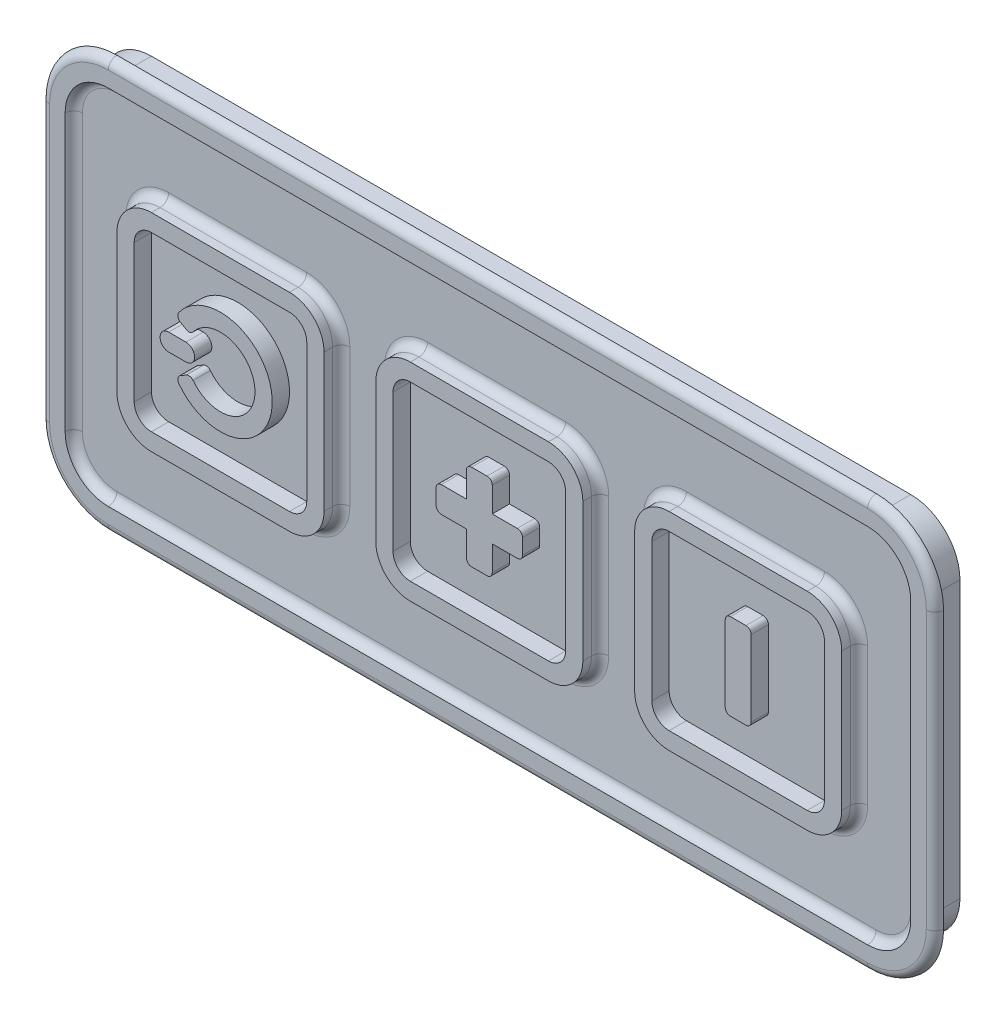
SolidWorks part; units mm, degrees
ref_plane "前视基准面" through (0, 0, 0) normal (0, 0, 1) x (1, 0, 0)
ref_plane "上视基准面" through (0, 0, 0) normal (0, 1, 0) x (1, 0, 0)
ref_plane "右视基准面" through (0, 0, 0) normal (1, 0, 0) x (0, 0, -1)
sketch "草图1" plane through (0, 0, 0) normal (0, 0, 1) x (1, 0, 0)
  line L8 (26.456, 8) -> (26.456, -8)
  line L9 (29.356, -10.9) -> (73.356, -10.9)
  line L10 (76.256, -8) -> (76.256, 8)
  line L11 (73.356, 10.9) -> (29.356, 10.9)
  arc A8 (26.456, -8) -> (29.356, -10.9) centre (29.356, -8) ccw
  arc A9 (73.356, -10.9) -> (76.256, -8) centre (73.356, -8) ccw
  arc A10 (76.256, 8) -> (73.356, 10.9) centre (73.356, 8) ccw
  arc A11 (29.356, 10.9) -> (26.456, 8) centre (29.356, 8) ccw
extrude "凸台-拉伸1" add sketch "草图1" against normal blind 2
sketch "草图2" plane through (0, 0, 0) normal (0, 0, 1) x (1, 0, 0)
  line L4 (26.856, 8) -> (26.856, -8)
  line L5 (29.356, -10.5) -> (73.356, -10.5)
  line L6 (75.856, -8) -> (75.856, 8)
  line L7 (73.356, 10.5) -> (29.356, 10.5)
  line L8 (25.456, 8) -> (25.456, -8)
  line L9 (25.456, 8) -> (25.456, -8)
  line L10 (29.356, -11.9) -> (73.356, -11.9)
  line L11 (29.356, -11.9) -> (73.356, -11.9)
  line L20 (25.356, 8) -> (25.356, -8) construction
  line L21 (29.356, -12) -> (73.356, -12) construction
  line L22 (77.356, -8) -> (77.356, 8) construction
  line L23 (73.356, 12) -> (29.356, 12) construction
  line L24 (77.256, -8) -> (77.256, 8)
  line L25 (77.256, -8) -> (77.256, 8)
  line L26 (73.356, 11.9) -> (29.356, 11.9)
  line L27 (73.356, 11.9) -> (29.356, 11.9)
  arc A4 (26.856, -8) -> (29.356, -10.5) centre (29.356, -8) ccw
  arc A5 (73.356, -10.5) -> (75.856, -8) centre (73.356, -8) ccw
  arc A6 (75.856, 8) -> (73.356, 10.5) centre (73.356, 8) ccw
  arc A7 (29.356, 10.5) -> (26.856, 8) centre (29.356, 8) ccw
  arc A8 (29.356, 11.9) -> (25.456, 8) centre (29.356, 8) ccw
  arc A9 (29.356, 11.9) -> (25.456, 8) centre (29.356, 8) ccw
  arc A10 (25.456, -8) -> (29.356, -11.9) centre (29.356, -8) ccw
  arc A11 (25.456, -8) -> (29.356, -11.9) centre (29.356, -8) ccw
  arc A20 (29.356, 12) -> (25.356, 8) centre (29.356, 8) ccw construction
  arc A21 (25.356, -8) -> (29.356, -12) centre (29.356, -8) ccw construction
  arc A22 (73.356, -12) -> (77.356, -8) centre (73.356, -8) ccw construction
  arc A23 (77.356, 8) -> (73.356, 12) centre (73.356, 8) ccw construction
  arc A24 (73.356, -11.9) -> (77.256, -8) centre (73.356, -8) ccw
  arc A25 (73.356, -11.9) -> (77.256, -8) centre (73.356, -8) ccw
  arc A26 (77.256, 8) -> (73.356, 11.9) centre (73.356, 8) ccw
  arc A27 (77.256, 8) -> (73.356, 11.9) centre (73.356, 8) ccw
  dimension "D1" = 1
  dimension "D2" = 1.5
extrude "凸台-拉伸2" add sketch "草图2" along normal blind 0.5
sketch "草图3" plane through (0, 0, -2) normal (0, 0, -1) x (-1, 0, 0)
  line L8 (-29.356, 9.9) -> (-73.356, 9.9)
  line L9 (-29.356, 9.9) -> (-73.356, 9.9)
  line L10 (-75.256, 8) -> (-75.256, -8)
  line L11 (-75.256, 8) -> (-75.256, -8)
  line L16 (-73.356, -9.9) -> (-29.356, -9.9)
  line L17 (-73.356, -9.9) -> (-29.356, -9.9)
  line L18 (-27.456, -8) -> (-27.456, 8)
  line L19 (-27.456, -8) -> (-27.456, 8)
  arc A8 (-27.456, 8) -> (-29.356, 9.9) centre (-29.356, 8) ccw
  arc A9 (-27.456, 8) -> (-29.356, 9.9) centre (-29.356, 8) ccw
  arc A10 (-73.356, 9.9) -> (-75.256, 8) centre (-73.356, 8) ccw
  arc A11 (-73.356, 9.9) -> (-75.256, 8) centre (-73.356, 8) ccw
  arc A16 (-75.256, -8) -> (-73.356, -9.9) centre (-73.356, -8) ccw
  arc A17 (-75.256, -8) -> (-73.356, -9.9) centre (-73.356, -8) ccw
  arc A18 (-29.356, -9.9) -> (-27.456, -8) centre (-29.356, -8) ccw
  arc A19 (-29.356, -9.9) -> (-27.456, -8) centre (-29.356, -8) ccw
  dimension "D1" = 1
extrude "切除-拉伸1" cut sketch "草图3" against normal blind 1
sketch "草图4" plane through (0, 0, 0) normal (0, 0, 1) x (1, 0, 0)
  line L0 (27.356, 0) -> (75.356, 0) construction
  line L3 (32.356, 6) -> (40.356, 6)
  line L4 (32.356, 5) -> (40.356, 5)
  line L5 (31.356, 4) -> (31.356, -4)
  line L6 (32.356, -5) -> (40.356, -5)
  line L7 (41.356, 4) -> (41.356, -4)
  line L8 (31.356, 5) -> (41.356, -5) construction
  line L9 (31.356, -5) -> (41.356, 5) construction
  line L10 (47.356, 5) -> (55.356, 5)
  line L11 (46.356, 4) -> (46.356, -4)
  line L12 (47.356, -5) -> (55.356, -5)
  line L13 (56.356, 4) -> (56.356, -4)
  line L14 (46.356, 5) -> (56.356, -5) construction
  line L15 (46.356, -5) -> (56.356, 5) construction
  line L16 (62.356, 5) -> (70.356, 5)
  line L17 (61.356, 4) -> (61.356, -4)
  line L18 (62.356, -5) -> (70.356, -5)
  line L19 (71.356, 4) -> (71.356, -4)
  line L20 (61.356, 5) -> (71.356, -5) construction
  line L21 (61.356, -5) -> (71.356, 5) construction
  line L22 (42.356, 4) -> (42.356, -4)
  line L23 (32.356, -6) -> (40.356, -6)
  line L24 (30.356, 4) -> (30.356, -4)
  line L25 (47.356, 6) -> (55.356, 6)
  line L26 (57.356, 4) -> (57.356, -4)
  line L27 (47.356, -6) -> (55.356, -6)
  line L28 (45.356, 4) -> (45.356, -4)
  line L29 (62.356, 6) -> (70.356, 6)
  line L30 (72.356, 4) -> (72.356, -4)
  line L31 (62.356, -6) -> (70.356, -6)
  line L32 (60.356, 4) -> (60.356, -4)
  arc A0 (70.356, 5) -> (71.356, 4) centre (70.356, 4) cw
  arc A1 (70.356, -5) -> (71.356, -4) centre (70.356, -4) ccw
  arc A2 (61.356, -4) -> (62.356, -5) centre (62.356, -4) ccw
  arc A3 (62.356, 5) -> (61.356, 4) centre (62.356, 4) ccw
  arc A4 (55.356, 5) -> (56.356, 4) centre (55.356, 4) cw
  arc A5 (55.356, -5) -> (56.356, -4) centre (55.356, -4) ccw
  arc A6 (46.356, -4) -> (47.356, -5) centre (47.356, -4) ccw
  arc A7 (47.356, 5) -> (46.356, 4) centre (47.356, 4) ccw
  arc A8 (40.356, 5) -> (41.356, 4) centre (40.356, 4) cw
  arc A9 (40.356, -5) -> (41.356, -4) centre (40.356, -4) ccw
  arc A10 (31.356, -4) -> (32.356, -5) centre (32.356, -4) ccw
  arc A11 (32.356, 5) -> (31.356, 4) centre (32.356, 4) ccw
  arc A12 (40.356, 6) -> (42.356, 4) centre (40.356, 4) cw
  arc A13 (40.356, -6) -> (42.356, -4) centre (40.356, -4) ccw
  arc A14 (30.356, -4) -> (32.356, -6) centre (32.356, -4) ccw
  arc A15 (32.356, 6) -> (30.356, 4) centre (32.356, 4) ccw
  arc A16 (55.356, 6) -> (57.356, 4) centre (55.356, 4) cw
  arc A17 (55.356, -6) -> (57.356, -4) centre (55.356, -4) ccw
  arc A18 (45.356, -4) -> (47.356, -6) centre (47.356, -4) ccw
  arc A19 (47.356, 6) -> (45.356, 4) centre (47.356, 4) ccw
  arc A20 (70.356, 6) -> (72.356, 4) centre (70.356, 4) cw
  arc A21 (70.356, -6) -> (72.356, -4) centre (70.356, -4) ccw
  arc A22 (60.356, -4) -> (62.356, -6) centre (62.356, -4) ccw
  arc A23 (62.356, 6) -> (60.356, 4) centre (62.356, 4) ccw
  point P6 (36.356, 0)
  point P11 (51.356, 0)
  point P16 (66.356, 0)
  dimension "D9" = 1
  dimension "D1" = 10
  dimension "D2" = 10
  dimension "D3" = 10
  dimension "D4" = 10
  dimension "D5" = 10
  dimension "D6" = 10
  dimension "D7" = 15
  dimension "D8" = 15
  dimension "D10" = 1
extrude "凸台-拉伸3" add sketch "草图4" along normal blind 1
fillet "圆角3" radius 0.5 32 edges at (60.9417, -5.4142, 0) (66.356, -6, 0) (71.7702, -5.4142, 0) (72.356, 0, 0) (71.7702, 5.4142, 0) (66.356, 6, 0) (60.9417, 5.4142, 0) (60.356, 0, 0) (30.9417, -5.4142, 0) (36.356, -6, 0) (41.7702, -5.4142, 0) (42.356, 0, 0) (41.7702, 5.4142, 0) (36.356, 6, 0) (30.9417, 5.4142, 0) (30.356, 0, 0) (45.9417, -5.4142, 0) (51.356, -6, 0) (56.7702, -5.4142, 0) (57.356, 0, 0) (56.7702, 5.4142, 0) (51.356, 6, 0) (45.9417, 5.4142, 0) (45.356, 0, 0) (51.356, 10.5, 0) (75.1237, 9.7678, 0) (75.856, 0, 0) (75.1237, -9.7678, 0) (51.356, -10.5, 0) (27.5882, -9.7678, 0) (26.856, 0, 0) (27.5882, 9.7678, 0)
sketch "草图5" plane through (0, 0, 0) normal (0, 0, 1) x (1, 0, 0)
  line L0 (61.856, 0) -> (70.856, 0) construction
  line L7 (46.856, 0) -> (48.856, 0) construction
  line L9 (66.356, -4.5) -> (66.356, 4.5) construction
  line L11 (65.906, -2.5) -> (66.806, -2.5)
  line L12 (65.606, -2.2) -> (65.606, 2.2)
  line L13 (65.906, 2.5) -> (66.806, 2.5)
  line L14 (67.106, -2.2) -> (67.106, 2.2)
  line L15 (65.606, -2.5) -> (67.106, 2.5) construction
  line L16 (65.606, 2.5) -> (67.106, -2.5) construction
  line L19 (55.856, 0) -> (51.356, -4.5) construction
  line L21 (51.356, -4.5) -> (51.356, -2.5) construction
  line L23 (31.856, 0) -> (34.856, 0) construction
  line L24 (50.906, -2.5) -> (51.806, -2.5)
  line L25 (50.606, -2.2) -> (50.606, -0.75)
  line L26 (50.906, 2.5) -> (51.806, 2.5)
  line L27 (52.106, -2.2) -> (52.106, -0.75)
  line L30 (49.156, -0.75) -> (50.606, -0.75)
  line L31 (48.856, -0.45) -> (48.856, 0.45)
  line L32 (49.156, 0.75) -> (50.606, 0.75)
  line L33 (53.856, -0.45) -> (53.856, 0.45)
  line L36 (33.356, 0) -> (34.356, 0) construction
  line L37 (33.356, 0.5) -> (34.356, 0.5)
  line L38 (52.106, -0.75) -> (53.556, -0.75)
  line L39 (33.356, -0.5) -> (34.356, -0.5)
  line L40 (53.856, 0) -> (55.856, 0) construction
  line L41 (52.106, 0.75) -> (52.106, 2.2)
  line L42 (34.3811, -1.1402) -> (34.0322, -1.3416)
  line L43 (51.356, 2.5) -> (51.356, 4.5) construction
  line L44 (34.3811, 1.1402) -> (34.0322, 1.3416)
  line L45 (50.606, 0.75) -> (50.606, 2.2)
  line L47 (52.106, 0.75) -> (53.556, 0.75)
  line L50 (36.356, -4.5) -> (36.356, 4.5) construction
  line L56 (36.356, 0) -> (40.856, 0) construction
  arc A8 (34.7691, -1.2174) -> (34.7691, 1.2174) centre (36.356, 0) ccw
  arc A9 (33.9406, -1.7794) -> (33.9406, 1.7794) centre (36.356, 0) ccw
  arc A10 (33.356, 0.5) -> (33.356, -0.5) centre (33.356, 0) ccw
  arc A11 (34.356, -0.5) -> (34.356, 0.5) centre (34.356, 0) ccw
  arc A12 (34.0322, -1.3416) -> (33.9406, -1.7794) centre (34.1822, -1.6014) ccw
  arc A13 (34.3811, -1.1402) -> (34.7691, -1.2174) centre (34.5311, -1.4) cw
  arc A14 (34.3811, 1.1402) -> (34.7691, 1.2174) centre (34.5311, 1.4) ccw
  arc A15 (34.0322, 1.3416) -> (33.9406, 1.7794) centre (34.1822, 1.6014) cw
  arc A16 (66.806, -2.5) -> (67.106, -2.2) centre (66.806, -2.2) ccw
  arc A17 (65.906, -2.5) -> (65.606, -2.2) centre (65.906, -2.2) cw
  arc A18 (66.806, 2.5) -> (67.106, 2.2) centre (66.806, 2.2) cw
  arc A19 (65.606, 2.2) -> (65.906, 2.5) centre (65.906, 2.2) cw
  arc A20 (48.856, 0.45) -> (49.156, 0.75) centre (49.156, 0.45) cw
  arc A21 (49.156, -0.75) -> (48.856, -0.45) centre (49.156, -0.45) cw
  arc A22 (50.906, -2.5) -> (50.606, -2.2) centre (50.906, -2.2) cw
  arc A23 (51.806, -2.5) -> (52.106, -2.2) centre (51.806, -2.2) ccw
  arc A24 (53.556, -0.75) -> (53.856, -0.45) centre (53.556, -0.45) ccw
  arc A25 (53.556, 0.75) -> (53.856, 0.45) centre (53.556, 0.45) cw
  arc A26 (51.806, 2.5) -> (52.106, 2.2) centre (51.806, 2.2) cw
  arc A27 (50.606, 2.2) -> (50.906, 2.5) centre (50.906, 2.2) cw
  point P12 (66.356, 0)
  point P29 (51.356, 0)
  point P34 (51.356, 0)
  point P64 (33.856, 0)
  point P74 (33.7579, -1.5)
  point P81 (33.7579, 1.5)
  point P84 (48.856, 0.75)
  point P87 (48.856, -0.75)
  point P90 (50.606, -2.5)
  point P93 (52.106, -2.5)
  point P98 (53.856, 0.75)
  point P101 (52.106, 2.5)
  dimension "D7" = 4
  dimension "D8" = 1
  dimension "D10" = 30
  dimension "D11" = 0.3
  dimension "D12" = 0.3
  dimension "D1" = 5
  dimension "D2" = 1.5
  dimension "D3" = 5
  dimension "D4" = 5
  dimension "D5" = 1.5
  dimension "D6" = 1.5
  dimension "D9" = 1
extrude "凸台-拉伸4" add sketch "草图5" along normal blind 1
sketch "草图6" plane through (0, 0, -2) normal (0, 0, -1) x (-1, 0, 0)
  line L4 (-29.356, 12.85) -> (-73.356, 12.85)
  line L5 (-78.206, 8) -> (-78.206, -8)
  line L6 (-73.356, -12.85) -> (-29.356, -12.85)
  line L7 (-24.506, -8) -> (-24.506, 8)
  line L8 (-29.356, 10.85) -> (-73.356, 10.85)
  line L9 (-76.206, 8) -> (-76.206, -8)
  line L10 (-73.356, -10.85) -> (-29.356, -10.85)
  line L11 (-26.506, -8) -> (-26.506, 8)
  line L12 (-29.356, 10.85) -> (-73.356, 10.85)
  line L13 (-76.206, 8) -> (-76.206, -8)
  line L14 (-73.356, -10.85) -> (-29.356, -10.85)
  line L15 (-26.506, -8) -> (-26.506, 8)
  arc A4 (-73.356, 12.85) -> (-78.206, 8) centre (-73.356, 8) ccw
  arc A5 (-78.206, -8) -> (-73.356, -12.85) centre (-73.356, -8) ccw
  arc A6 (-29.356, -12.85) -> (-24.506, -8) centre (-29.356, -8) ccw
  arc A7 (-24.506, 8) -> (-29.356, 12.85) centre (-29.356, 8) ccw
  arc A8 (-26.506, 8) -> (-29.356, 10.85) centre (-29.356, 8) ccw
  arc A9 (-73.356, 10.85) -> (-76.206, 8) centre (-73.356, 8) ccw
  arc A10 (-76.206, -8) -> (-73.356, -10.85) centre (-73.356, -8) ccw
  arc A11 (-29.356, -10.85) -> (-26.506, -8) centre (-29.356, -8) ccw
  arc A12 (-26.506, 8) -> (-29.356, 10.85) centre (-29.356, 8) ccw
  arc A13 (-73.356, 10.85) -> (-76.206, 8) centre (-73.356, 8) ccw
  arc A14 (-76.206, -8) -> (-73.356, -10.85) centre (-73.356, -8) ccw
  arc A15 (-29.356, -10.85) -> (-26.506, -8) centre (-29.356, -8) ccw
  dimension "D1" = 0.05
  dimension "D2" = 2
extrude "切除-拉伸2" cut sketch "草图6" against normal blind 2
fillet "圆角5" radius 0.5 8 edges at (26.5982, -10.7577, 0.5) (25.456, 0, 0.5) (26.5982, 10.7577, 0.5) (51.356, 11.9, 0.5) (76.1137, 10.7577, 0.5) (77.256, 0, 0.5) (76.1137, -10.7577, 0.5) (51.356, -11.9, 0.5)
sketch "草图7" plane through (0, 0, -1) normal (0, 0, -1) x (-1, 0, 0)
  line L0 (-75.256, 0) -> (-27.456, 0) construction
  line L1 (-75.256, 8) -> (-75.256, -8) construction
  line L2 (-27.456, -8) -> (-27.456, 8) construction
  line L3 (-75.5142, 0) -> (-27.1977, 0) construction
  line L4 (-29.356, 9.9) -> (-73.356, 9.9) construction
  line L5 (-51.356, 9.9) -> (-51.356, -9.9) construction
  line L6 (-73.356, -9.9) -> (-29.356, -9.9) construction
  line L7 (-70.5142, 6.0791) -> (-62.5142, 6.0791)
  line L8 (-70.5142, 5) -> (-62.5142, 5)
  line L9 (-71.5142, 4) -> (-71.5142, -4)
  line L10 (-70.5142, -5) -> (-62.5142, -5)
  line L11 (-61.5142, 4) -> (-61.5142, -4)
  line L12 (-71.5142, 5) -> (-61.5142, -5) construction
  line L13 (-71.5142, -5) -> (-61.5142, 5) construction
  line L14 (-55.356, 5) -> (-47.356, 5)
  line L15 (-56.356, 4) -> (-56.356, -4)
  line L16 (-55.356, -5) -> (-47.356, -5)
  line L17 (-46.356, 4) -> (-46.356, -4)
  line L18 (-56.356, 5) -> (-46.356, -5) construction
  line L19 (-56.356, -5) -> (-46.356, 5) construction
  line L20 (-40.5142, 5) -> (-32.5142, 5)
  line L21 (-41.5142, 4) -> (-41.5142, -4)
  line L22 (-40.5142, -5) -> (-32.5142, -5)
  line L23 (-31.5142, 4) -> (-31.5142, -4)
  line L24 (-41.5142, 5) -> (-31.5142, -5) construction
  line L25 (-41.5142, -5) -> (-31.5142, 5) construction
  line L26 (-60.5142, 4.0791) -> (-60.5142, -3.9209)
  line L27 (-70.5142, -5.9209) -> (-62.5142, -5.9209)
  line L28 (-72.5142, 4.0791) -> (-72.5142, -3.9209)
  line L29 (-55.5142, 6.0791) -> (-47.5142, 6.0791)
  line L30 (-45.5142, 4.0791) -> (-45.5142, -3.9209)
  line L31 (-55.5142, -5.9209) -> (-47.5142, -5.9209)
  line L32 (-57.5142, 4.0791) -> (-57.5142, -3.9209)
  line L33 (-40.5142, 6.0791) -> (-32.5142, 6.0791)
  line L34 (-30.5142, 4.0791) -> (-30.5142, -3.9209)
  line L35 (-40.5142, -5.9209) -> (-32.5142, -5.9209)
  line L36 (-42.5142, 4.0791) -> (-42.5142, -3.9209)
  arc A0 (-32.5142, 5) -> (-31.5142, 4) centre (-32.5142, 4) cw
  arc A1 (-32.5142, -5) -> (-31.5142, -4) centre (-32.5142, -4) ccw
  arc A2 (-41.5142, -4) -> (-40.5142, -5) centre (-40.5142, -4) ccw
  arc A3 (-40.5142, 5) -> (-41.5142, 4) centre (-40.5142, 4) ccw
  arc A4 (-47.356, 5) -> (-46.356, 4) centre (-47.356, 4) cw
  arc A5 (-47.356, -5) -> (-46.356, -4) centre (-47.356, -4) ccw
  arc A6 (-56.356, -4) -> (-55.356, -5) centre (-55.356, -4) ccw
  arc A7 (-55.356, 5) -> (-56.356, 4) centre (-55.356, 4) ccw
  arc A8 (-62.5142, 5) -> (-61.5142, 4) centre (-62.5142, 4) cw
  arc A9 (-62.5142, -5) -> (-61.5142, -4) centre (-62.5142, -4) ccw
  arc A10 (-71.5142, -4) -> (-70.5142, -5) centre (-70.5142, -4) ccw
  arc A11 (-70.5142, 5) -> (-71.5142, 4) centre (-70.5142, 4) ccw
  arc A12 (-62.5142, 6.0791) -> (-60.5142, 4.0791) centre (-62.5142, 4.0791) cw
  arc A13 (-62.5142, -5.9209) -> (-60.5142, -3.9209) centre (-62.5142, -3.9209) ccw
  arc A14 (-72.5142, -3.9209) -> (-70.5142, -5.9209) centre (-70.5142, -3.9209) ccw
  arc A15 (-70.5142, 6.0791) -> (-72.5142, 4.0791) centre (-70.5142, 4.0791) ccw
  arc A16 (-47.5142, 6.0791) -> (-45.5142, 4.0791) centre (-47.5142, 4.0791) cw
  arc A17 (-47.5142, -5.9209) -> (-45.5142, -3.9209) centre (-47.5142, -3.9209) ccw
  arc A18 (-57.5142, -3.9209) -> (-55.5142, -5.9209) centre (-55.5142, -3.9209) ccw
  arc A19 (-55.5142, 6.0791) -> (-57.5142, 4.0791) centre (-55.5142, 4.0791) ccw
  arc A20 (-32.5142, 6.0791) -> (-30.5142, 4.0791) centre (-32.5142, 4.0791) cw
  arc A21 (-32.5142, -5.9209) -> (-30.5142, -3.9209) centre (-32.5142, -3.9209) ccw
  arc A22 (-42.5142, -3.9209) -> (-40.5142, -5.9209) centre (-40.5142, -3.9209) ccw
  arc A23 (-40.5142, 6.0791) -> (-42.5142, 4.0791) centre (-40.5142, 4.0791) ccw
  point P15 (-66.5142, 0)
  point P20 (-51.356, 0)
  point P25 (-36.5142, 0)
  dimension "D7" = 1
  dimension "D1" = 10
  dimension "D2" = 10
  dimension "D3" = 10
  dimension "D4" = 10
  dimension "D5" = 10
  dimension "D6" = 10
  dimension "D8" = 0
  dimension "D9" = 0
extrude "凸台-拉伸5" add sketch "草图7" along normal blind 1
fillet "圆角6" radius 0.5 56 edges at (31.5142, 0, -1) (31.8071, -4.7071, -1) (36.5142, -5, -1) (41.2213, -4.7071, -1) (41.5142, 0, -1) (41.2213, 4.7071, -1) (36.5142, 5, -1) (31.8071, 4.7071, -1) (46.356, 0, -1) (46.6489, -4.7071, -1) (51.356, -5, -1) (56.0631, -4.7071, -1) (56.356, 0, -1) (56.0631, 4.7071, -1) (51.356, 5, -1) (46.6489, 4.7071, -1) (61.5142, 0, -1) (61.8071, -4.7071, -1) (66.5142, -5, -1) (71.2213, -4.7071, -1) (71.5142, 0, -1) (71.2213, 4.7071, -1) (66.5142, 5, -1) (61.8071, 4.7071, -1) (41.9284, -5.3351, -1) (36.5142, -5.9209, -1) (31.1, -5.3351, -1) (30.5142, 0.0791, -1) (31.1, 5.4933, -1) (36.5142, 6.0791, -1) (41.9284, 5.4933, -1) (42.5142, 0.0791, -1) (71.9284, -5.3351, -1) (66.5142, -5.9209, -1) (61.1, -5.3351, -1) (60.5142, 0.0791, -1) (61.1, 5.4933, -1) (66.5142, 6.0791, -1) (71.9284, 5.4933, -1) (72.5142, 0.0791, -1) (27.456, 0, -1) (28.0125, -9.3435, -1) (51.356, -9.9, -1) (74.6995, -9.3435, -1) (75.256, 0, -1) (74.6995, 9.3435, -1) (51.356, 9.9, -1) (28.0125, 9.3435, -1) (56.9284, -5.3351, -1) (51.5142, -5.9209, -1) (46.1, -5.3351, -1) (45.5142, 0.0791, -1) (46.1, 5.4933, -1) (51.5142, 6.0791, -1) (56.9284, 5.4933, -1) (57.5142, 0.0791, -1)
